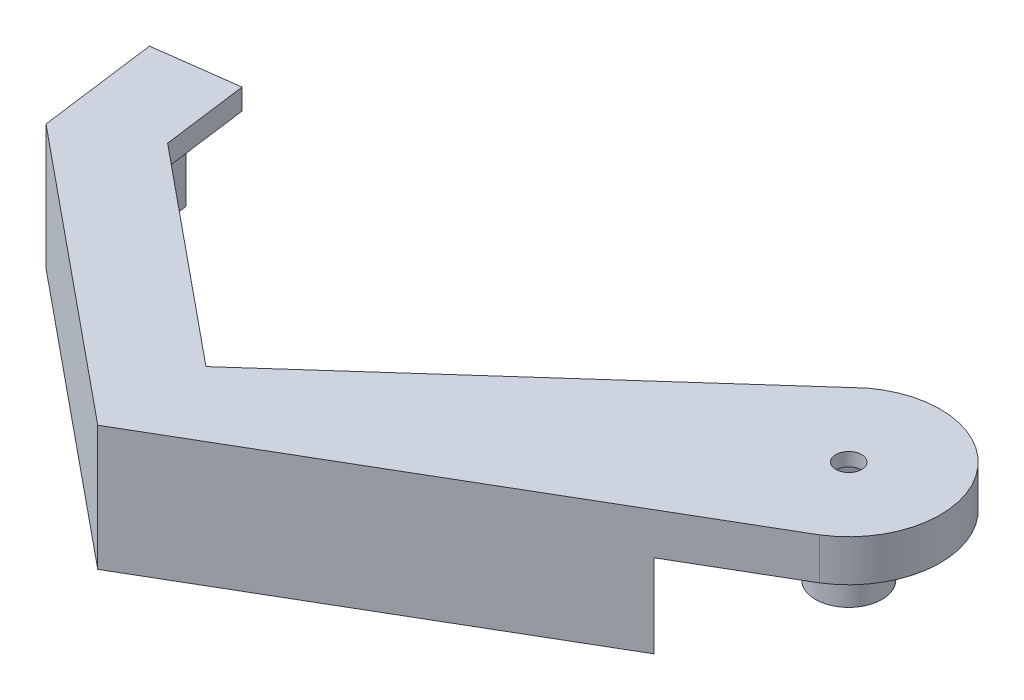
SolidWorks part; units mm, degrees
ref_plane "Front Plane" through (0, 0, 0) normal (0, 0, 1) x (1, 0, 0)
ref_plane "Top Plane" through (0, 0, 0) normal (0, 1, 0) x (1, 0, 0)
ref_plane "Right Plane" through (0, 0, 0) normal (1, 0, 0) x (0, 0, -1)
sketch "Sketch1" plane through (0, 0, 0) normal (0, 1, 0) x (1, 0, 0)
  circle A0 centre (0, 0) radius 10.3349
  dimension "D1" = 20.6698
extrude "Boss-Extrude1" add sketch "Sketch1" along normal blind 4
sketch "Sketch2" plane through (0, 0, 0) normal (0, -1, 0) x (1, 0, 0)
  circle A0 centre (0, 0) radius 4
other "Move Face1" flip direction yes face at (0, 0, 10.3349) offset 3 parameters "D1"=3
sketch "Sketch5" plane through (0, 3, 0) normal (0, -1, 0) x (1, 0, 0)
  line L0 (0, 0) -> (-48.7465, 34.9826) construction
  line L1 (-48.7465, 34.9826) -> (-78.7465, 10.3971) construction
  line L2 (0, 0) -> (-78.7465, 10.3971) construction
  line L3 (-78.7465, 10.3971) -> (-80.7177, -4.5326) construction
  line L5 (-75.4582, -2.5675) -> (-74.0969, 7.743)
  line L6 (-74.0969, 7.743) -> (-48.5447, 28.6834)
  line L10 (-48.9483, 41.2817) -> (-83.396, 13.0512)
  line L12 (-6.5426, -8.8428) -> (-48.5447, 28.6834)
  line L14 (-48.9483, 41.2817) -> (5.2508, 9.6659)
  line L15 (-75.4582, -2.5675) -> (-85.2869, -1.2698)
  line L16 (-85.2869, -1.2698) -> (-83.396, 13.0512)
  arc A3 (5.2508, 9.6659) -> (-6.5426, -8.8428) centre (0, 0) cw
  point P9 (-80.7177, -4.5326)
  point P15 (0, 0)
  dimension "D1" = 10.4
  dimension "D2" = 60
  dimension "D3" = 30
  dimension "D4" = 105
  dimension "D7" = 5
  dimension "D8" = 5
extrude "Boss-Extrude3" add sketch "Sketch5" along normal blind 5
sketch "Sketch6" plane through (0, -2, 0) normal (0, -1, 0) x (1, 0, 0)
  circle A0 centre (0, 0) radius 6.3
  dimension "D1" = 12.6
extrude "Boss-Extrude4" add sketch "Sketch6" along normal blind 0.3
other "Move Face2" flip direction yes face at (0, 4, 10.3349) offset 1 parameters "D1"=1
sketch "Sketch8" plane through (0, -2, 0) normal (0, -1, 0) x (1, 0, 0)
  line L0 (-85.2869, -1.2698) -> (-81.4016, -1.7828)
  line L1 (-85.2869, -1.2698) -> (-75.4582, -2.5675) construction
  line L2 (-81.4016, -1.7828) -> (-79.6672, 11.3539)
  line L3 (-79.6672, 11.3539) -> (-48.9483, 36.5285)
  line L6 (5.2508, 9.6659) -> (-48.9483, 41.2817) construction
  line L7 (-6.72, 16.6488) -> (-48.9483, 41.2817)
  line L8 (-48.9483, 41.2817) -> (-83.396, 13.0512)
  line L9 (-83.396, 13.0512) -> (-85.2869, -1.2698)
  line L10 (-12.814, 12.5754) -> (-48.9483, 36.5285)
  arc A0 (-6.72, 16.6488) -> (-12.814, 12.5754) centre (0, 0) ccw
extrude "Boss-Extrude5" add sketch "Sketch8" along normal blind 10
sketch "Sketch9" plane through (0, -2, 0) normal (0, -1, 0) x (1, 0, 0)
  line L0 (-48.5447, 28.6834) -> (-6.5426, -8.8428) construction
  line L1 (-17.906, 1.3097) -> (-75.4582, -2.5675)
  line L2 (-75.4582, -2.5675) -> (-81.4016, -1.7828)
  line L3 (-81.4016, -1.7828) -> (-79.6672, 11.3539)
  line L4 (-81.4016, -1.7828) -> (-79.6672, 11.3539) construction
  line L5 (-79.6672, 11.3539) -> (-48.9483, 36.5285)
  line L6 (-48.9483, 36.5285) -> (-12.814, 12.5754)
  arc A0 (-12.814, 12.5754) -> (-17.906, 1.3097) centre (0, 0) ccw
extrude "Cut-Extrude3" cut sketch "Sketch9" against normal blind 2.5
ref_axis "Axis2" through (0, -2, 0) along (0, 1, 0)
ref_plane "Plane1" through (0, 0, 0) normal (-0.5525, 0, -0.8335) x (-0.8335, 0, 0.5525)
sketch "Sketch10" plane through (0, 0, 0) normal (-0.5525, 0, -0.8335) x (-0.8335, 0, 0.5525)
  line L0 (17.9538, -2) -> (17.9538, 0.5) construction
  line L1 (17.9538, 1.01) -> (20.9538, 1.01)
  line L2 (17.9538, -1.99) -> (17.9538, 1.01)
  arc A0 (20.9538, 1.01) -> (17.9538, -1.99) centre (17.9538, 1.01) cw
  dimension "D1" = 3
revolve "Revolve3" add sketch "Sketch10" angle 360 about axis through (0, -2, 0) along (0, 1, 0) reverse direction yes
sketch "Sketch11" plane through (-7.2977, 0, -8.1681) normal (-0.6663, 0, -0.7457) x (-0.7457, 0, 0.6663)
  line L0 (-18.7151, -2) -> (-18.7151, 3)
  line L1 (55.3114, 3) -> (-1.0126, 3) construction
  line L2 (-18.7151, 3) -> (19.8414, 3)
  line L3 (19.8414, 3) -> (19.8414, -2)
  line L4 (19.8414, -2) -> (-18.7151, -2)
extrude "Cut-Extrude4" cut sketch "Sketch11" along normal blind 22
sketch "Sketch12" plane through (5.54, 0, 9.4972) normal (0.5039, 0, 0.8638) x (0.8638, 0, -0.5039)
  line L0 (-0.3347, 3) -> (-63.0811, 3) construction
  line L1 (-22.1385, 3) -> (21.5858, 3)
  line L2 (-22.1385, 3) -> (-22.1385, -8.2579)
  line L3 (-22.1385, -8.2579) -> (21.5858, -8.2579)
  line L4 (21.5858, 3) -> (21.5858, -8.2579)
extrude "Cut-Extrude5" cut sketch "Sketch12" along normal blind 23 body kept at (-75.4582, 3, -2.5675)
sketch "Sketch13" plane through (0, -2.3, 0) normal (0, -1, 0) x (1, 0, 0)
  circle A2 centre (0, 0) radius 4
  dimension "D1" = 8
extrude "Boss-Extrude6" add sketch "Sketch13" along normal blind 7
sketch "Sketch14" plane through (0, -9.3, 0) normal (0, -1, 0) x (1, 0, 0)
  circle A0 centre (0, 0) radius 1.55
  dimension "D1" = 3.1
extrude "Cut-Extrude6" cut sketch "Sketch14" against normal blind 14.3
ref_plane "Plane2" through (0, -1.1, 0) normal (0, -1, 0) x (-1, 0, 0)
sketch "Sketch15" plane through (0, -1.1, 0) normal (0, -1, 0) x (-1, 0, 0)
  line L1 (2.0704, -2.7773) -> (3.4404, 0.4043)
  line L2 (3.4404, 0.4043) -> (1.37, 3.1817)
  line L3 (1.37, 3.1817) -> (-2.0704, 2.7773)
  line L4 (-2.0704, 2.7773) -> (-3.4404, -0.4043)
  line L5 (-3.4404, -0.4043) -> (-1.37, -3.1817)
  line L6 (-1.37, -3.1817) -> (2.0704, -2.7773)
  circle A0 centre (0, 0) radius 3 construction
extrude "Cut-Extrude7" cut sketch "Sketch15" against normal blind 2.5
